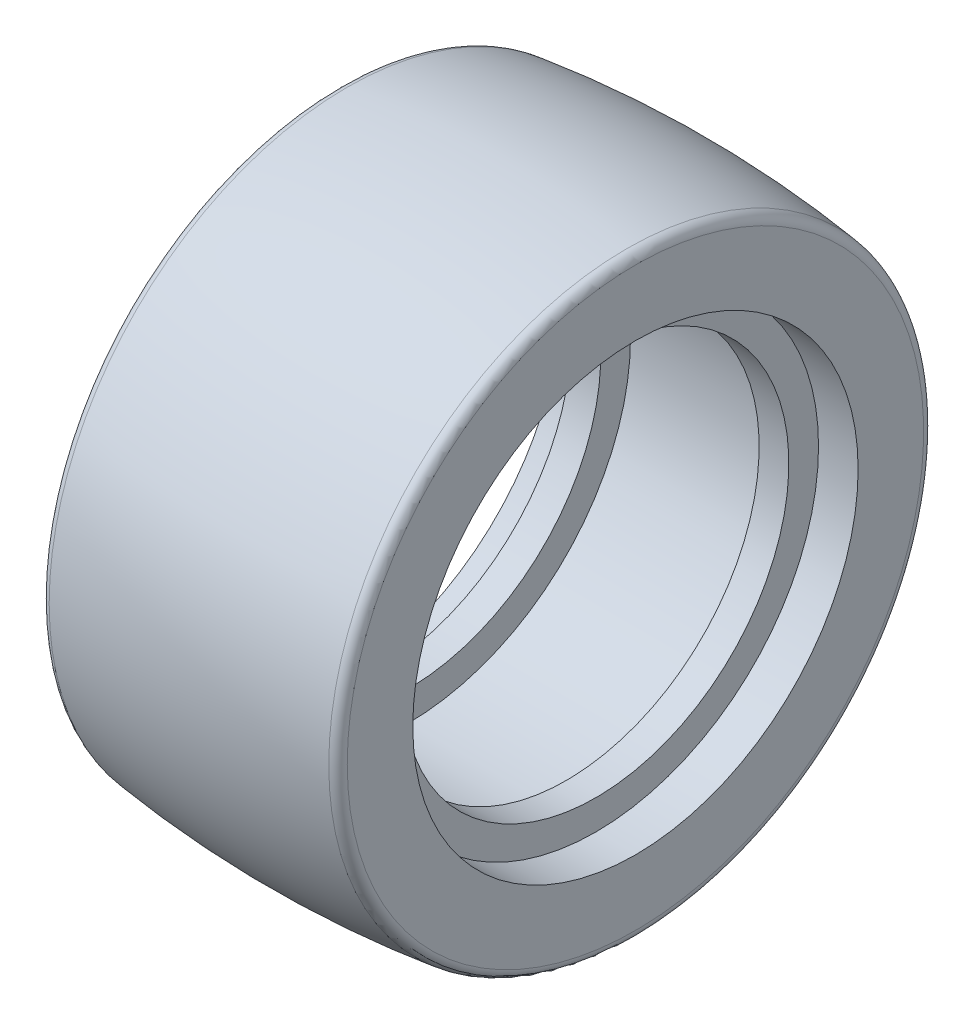
SolidWorks part; units mm, degrees
material "Силиконовая резина"
ref_plane "Спереди" through (0, 0, 0) normal (0, 0, 1) x (1, 0, 0)
ref_plane "Сверху" through (0, 0, 0) normal (0, 1, 0) x (1, 0, 0)
ref_plane "Справа" through (0, 0, 0) normal (1, 0, 0) x (0, 0, -1)
sketch "Эскиз1" plane through (0, 0, 0) normal (0, 0, 1) x (1, 0, 0)
  line L0 (-15, 22.5) -> (-11, 22.5)
  line L1 (-11, 22.5) -> (-11, 19.5)
  line L2 (-11, 19.5) -> (-8, 19.5)
  line L3 (-8, 19.5) -> (-8, 22.5)
  line L4 (-8, 22.5) -> (8, 22.5)
  line L5 (8, 22.5) -> (8, 19.5)
  line L6 (8, 19.5) -> (11, 19.5)
  line L7 (11, 19.5) -> (11, 22.5)
  line L8 (11, 22.5) -> (15, 22.5)
  line L9 (15, 22.5) -> (15, 30)
  line L10 (-15, 22.5) -> (-15, 30)
  line L11 (0, 29.5) -> (0, -2.8614) construction
  line L12 (-27.729, 0) -> (30.3752, 0) construction
  arc A0 (-15, 30) -> (15, 30) centre (0, -82) cw
  point P15 (0, 31)
  dimension "D1" = 4
  dimension "D2" = 3
  dimension "D3" = 3
  dimension "D4" = 30
  dimension "D5" = 7.5
  dimension "D7" = 45
  dimension "D6" = 8.5
revolve "Повернуть1" add sketch "Эскиз1" angle 360 about L12 region at (0, 26.2066, 0)
fillet "Скругление1" radius 1 2 edges at (15, 0, 30) (-15, 0, 30)
equation "\"D6@Эскиз1\"=\"D5@Эскиз1\"+1"
